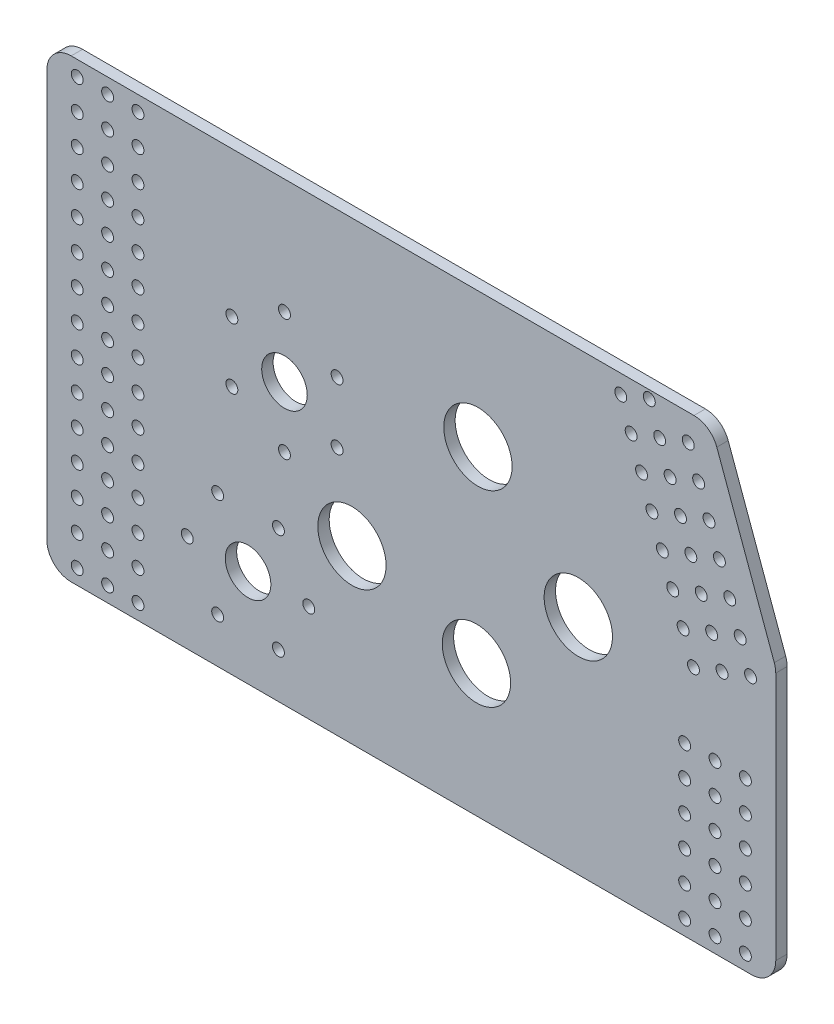
SolidWorks part; units mm, degrees
ref_plane "Front Plane" through (0, 0, 0) normal (0, 0, 1) x (1, 0, 0)
ref_plane "Top Plane" through (0, 0, 0) normal (0, 1, 0) x (1, 0, 0)
ref_plane "Right Plane" through (0, 0, 0) normal (1, 0, 0) x (0, 0, -1)
sketch "Sketch1" plane through (0, 0, 0) normal (0, 0, 1) x (1, 0, 0)
  line B0 (-152.4, 0) -> (152.4, 0)
  line B1 (152.4, 0) -> (152.4, 116.0843)
  line B2 (152.4, 116.0843) -> (125.3149, 190.5)
  line B3 (125.3149, 190.5) -> (-152.4, 190.5)
  line B4 (-152.4, 190.5) -> (-152.4, 0)
  circle B5 centre (-139.7, 184.15) radius 2.4892
  circle B6 centre (-127, 184.15) radius 2.4892
  circle B7 centre (-114.3, 184.15) radius 2.4892
  circle B8 centre (-127, 171.45) radius 2.4892
  circle B9 centre (-114.3, 171.45) radius 2.4892
  circle B10 centre (-127, 158.75) radius 2.4892
  circle B11 centre (-114.3, 158.75) radius 2.4892
  circle B12 centre (-127, 146.05) radius 2.4892
  circle B13 centre (-114.3, 146.05) radius 2.4892
  circle B14 centre (-127, 133.35) radius 2.4892
  circle B15 centre (-114.3, 133.35) radius 2.4892
  circle B16 centre (-127, 120.65) radius 2.4892
  circle B17 centre (-114.3, 120.65) radius 2.4892
  circle B18 centre (-127, 107.95) radius 2.4892
  circle B19 centre (-114.3, 107.95) radius 2.4892
  circle B20 centre (-127, 95.25) radius 2.4892
  circle B21 centre (-114.3, 95.25) radius 2.4892
  circle B22 centre (-127, 82.55) radius 2.4892
  circle B23 centre (-114.3, 82.55) radius 2.4892
  circle B24 centre (-127, 69.85) radius 2.4892
  circle B25 centre (-114.3, 69.85) radius 2.4892
  circle B26 centre (-127, 57.15) radius 2.4892
  circle B27 centre (-114.3, 57.15) radius 2.4892
  circle B28 centre (-127, 44.45) radius 2.4892
  circle B29 centre (-114.3, 44.45) radius 2.4892
  circle B30 centre (-127, 31.75) radius 2.4892
  circle B31 centre (-114.3, 31.75) radius 2.4892
  circle B32 centre (-127, 19.05) radius 2.4892
  circle B33 centre (-114.3, 19.05) radius 2.4892
  circle B34 centre (-127, 6.35) radius 2.4892
  circle B35 centre (-114.3, 6.35) radius 2.4892
  circle B36 centre (-139.7, 171.45) radius 2.4892
  circle B37 centre (-139.7, 158.75) radius 2.4892
  circle B38 centre (-139.7, 146.05) radius 2.4892
  circle B39 centre (-139.7, 133.35) radius 2.4892
  circle B40 centre (-139.7, 120.65) radius 2.4892
  circle B41 centre (-139.7, 107.95) radius 2.4892
  circle B42 centre (-139.7, 95.25) radius 2.4892
  circle B43 centre (-139.7, 82.55) radius 2.4892
  circle B44 centre (-139.7, 69.85) radius 2.4892
  circle B45 centre (-139.7, 57.15) radius 2.4892
  circle B46 centre (-139.7, 44.45) radius 2.4892
  circle B47 centre (-139.7, 31.75) radius 2.4892
  circle B48 centre (-139.7, 19.05) radius 2.4892
  circle B49 centre (-139.7, 6.35) radius 2.4892
  circle B50 centre (87.5907, 182.7494) radius 2.4892
  circle B51 centre (99.5248, 187.093) radius 2.4892
  circle B52 centre (115.8026, 179.5026) radius 2.4892
  circle B53 centre (91.9344, 170.8153) radius 2.4892
  circle B54 centre (103.8685, 175.1589) radius 2.4892
  circle B55 centre (120.1462, 167.5685) radius 2.4892
  circle B56 centre (96.278, 158.8812) radius 2.4892
  circle B57 centre (108.2121, 163.2248) radius 2.4892
  circle B58 centre (124.4899, 155.6344) radius 2.4892
  circle B59 centre (100.6217, 146.9471) radius 2.4892
  circle B60 centre (112.5558, 151.2907) radius 2.4892
  circle B61 centre (128.8335, 143.7003) radius 2.4892
  circle B62 centre (104.9653, 135.013) radius 2.4892
  circle B63 centre (116.8994, 139.3566) radius 2.4892
  circle B64 centre (133.1772, 131.7662) radius 2.4892
  circle B65 centre (109.309, 123.0789) radius 2.4892
  circle B66 centre (121.2431, 127.4226) radius 2.4892
  circle B67 centre (137.5208, 119.8321) radius 2.4892
  circle B68 centre (113.6526, 111.1448) radius 2.4892
  circle B69 centre (125.5867, 115.4885) radius 2.4892
  circle B70 centre (141.8645, 107.898) radius 2.4892
  circle B71 centre (117.9963, 99.2107) radius 2.4892
  circle B72 centre (129.9304, 103.5544) radius 2.4892
  circle B73 centre (146.2081, 95.9639) radius 2.4892
  circle B74 centre (114.3, 69.85) radius 2.4892
  circle B75 centre (127, 69.85) radius 2.4892
  circle B76 centre (139.7, 69.85) radius 2.4892
  circle B77 centre (114.3, 57.15) radius 2.4892
  circle B78 centre (127, 57.15) radius 2.4892
  circle B79 centre (139.7, 57.15) radius 2.4892
  circle B80 centre (114.3, 44.45) radius 2.4892
  circle B81 centre (127, 44.45) radius 2.4892
  circle B82 centre (139.7, 44.45) radius 2.4892
  circle B83 centre (114.3, 31.75) radius 2.4892
  circle B84 centre (127, 31.75) radius 2.4892
  circle B85 centre (139.7, 31.75) radius 2.4892
  circle B86 centre (114.3, 19.05) radius 2.4892
  circle B87 centre (127, 19.05) radius 2.4892
  circle B88 centre (139.7, 19.05) radius 2.4892
  circle B89 centre (114.3, 6.35) radius 2.4892
  circle B90 centre (127, 6.35) radius 2.4892
  circle B91 centre (139.7, 6.35) radius 2.4892
  circle B92 centre (11.8508, 132.0168) radius 14.2875
  circle B93 centre (-24.8197, 71.7449) radius 14.2875
  circle B94 centre (57.6351, 95.7125) radius 14.2875
  circle B95 centre (23.7546, 49.6787) radius 14.2875
  circle B96 centre (-65.2702, 36.9534) radius 9.525
  circle B97 centre (-65.2702, 106.5494) radius 9.525
  circle B98 centre (-65.2702, 131.9494) radius 2.4892
  circle B99 centre (-65.2702, 11.5534) radius 2.4892
  circle B100 centre (-43.2731, 119.2494) radius 2.4892
  circle B101 centre (-43.2731, 93.8494) radius 2.4892
  circle B102 centre (-65.2702, 81.1494) radius 2.4892
  circle B103 centre (-87.2672, 93.8494) radius 2.4892
  circle B104 centre (-87.2672, 119.2494) radius 2.4892
  circle B105 centre (-87.2672, 24.2534) radius 2.4892
  circle B106 centre (-87.2672, 49.6534) radius 2.4892
  circle B107 centre (-65.2702, 62.3534) radius 2.4892
  circle B108 centre (-43.2731, 49.6534) radius 2.4892
  circle B109 centre (-43.2731, 24.2534) radius 2.4892
sketch_block_instance "Block-InnerPlate-1"
sketch_block "Block-InnerPlate" parameters "D1"=4.9784, "D7"=4.9784, "D8"=4.9784, "D9"=4.9784, "D11"=4.9784, "D12"=4.9784, "D13"=4.9784, "D15"=19.05, "D16"=19.05, "D17"=28.575, "D18"=28.575, "D19"=28.575, "D20"=28.575, "D21"=4.9784, "D22"=4.9784, "D2"=6.35, "D3"=12.7, "D4"=12.7, "D5"=12.7, "D6"=6.35, "D10"=12.7, "D14"=12.7, "D23"=25.4, "D24"=25.4
extrude "Boss-Extrude1" add sketch "Sketch1" along normal blind 4.7625
sketch "Sketch2" plane through (0, 0, 4.7625) normal (0, 0, 1) x (1, 0, 0)
  circle A0 centre (146.2081, 95.9639) radius 2.4892
  dimension "D1" = 4.9784
extrude "Boss-Extrude2" add sketch "Sketch2" against normal blind 3.175
fillet "Fillet1" radius 10.16 5 edges at (-152.4, 0, 2.3813) (152.4, 0, 2.3813) (152.4, 116.0843, 2.3813) (125.3149, 190.5, 2.3813) (-152.4, 190.5, 2.3813)
sketch "Sketch3" plane through (0, 0, 4.7625) normal (0, 0, 1) x (1, 0, 0)
  line L0 (-65.2702, 106.5494) -> (-39.8702, 106.5494) construction
  line L1 (-65.2702, 36.9534) -> (-39.8702, 36.9534) construction
  circle A0 centre (-65.2702, 106.5494) radius 9.525
  circle A1 centre (-39.8702, 106.5494) radius 2.4892
  circle A2 centre (-52.5702, 84.5524) radius 2.4892
  circle A3 centre (-77.9702, 84.5524) radius 2.4892
  circle A4 centre (-90.6702, 106.5494) radius 2.4892
  circle A5 centre (-77.9702, 128.5465) radius 2.4892
  circle A6 centre (-52.5702, 128.5465) radius 2.4892
  circle A7 centre (-65.2702, 36.9534) radius 9.525
  circle A8 centre (-39.8702, 36.9534) radius 2.4892
  circle A9 centre (-52.5702, 14.9564) radius 2.4892
  circle A10 centre (-77.9702, 14.9564) radius 2.4892
  circle A11 centre (-90.6702, 36.9534) radius 2.4892
  circle A12 centre (-77.9702, 58.9505) radius 2.4892
  circle A13 centre (-52.5702, 58.9505) radius 2.4892
  dimension "D1" = 19.05
  dimension "D2" = 4.9784
  dimension "D7" = 19.05
  dimension "D8" = 4.9784
  dimension "D3" = 25.4
  dimension "D5" = 25.4
  dimension "D6" = 25.4
  dimension "D9" = 25.4
  dimension "D11" = 25.4
  dimension "D4" = 6
  dimension "D10" = 6
extrude "Cut-Extrude1" cut sketch "Sketch3" against normal blind 3.175
sketch "Sketch4" plane through (0, 0, 4.7625) normal (0, 0, 1) x (1, 0, 0)
  circle A0 centre (-65.2702, 131.9494) radius 2.4892
  circle A1 centre (-43.2731, 119.2494) radius 2.4892
  circle A2 centre (-43.2731, 93.8494) radius 2.4892
  circle A3 centre (-65.2702, 81.1494) radius 2.4892
  circle A4 centre (-87.2672, 93.8494) radius 2.4892
  circle A5 centre (-87.2672, 119.2494) radius 2.4892
  circle A6 centre (-65.2702, 62.3534) radius 2.4892
  circle A7 centre (-43.2731, 49.6534) radius 2.4892
  circle A8 centre (-43.2731, 24.2534) radius 2.4892
  circle A9 centre (-65.2702, 11.5534) radius 2.4892
  circle A10 centre (-87.2672, 24.2534) radius 2.4892
  circle A11 centre (-87.2672, 49.6534) radius 2.4892
  dimension "D1" = 4.9784
  dimension "D2" = 4.9784
  dimension "D3" = 4.9784
  dimension "D4" = 4.9784
  dimension "D5" = 4.9784
  dimension "D6" = 4.9784
  dimension "D7" = 4.9784
  dimension "D8" = 4.9784
  dimension "D9" = 4.9784
  dimension "D10" = 4.9784
  dimension "D11" = 4.9784
  dimension "D12" = 4.9784
extrude "Boss-Extrude3" add sketch "Sketch4" against normal blind 3.175
sketch "Sketch6" plane through (0, 0, 4.7625) normal (0, 0, 1) x (1, 0, 0)
  circle A0 centre (23.7546, 49.6787) radius 14.2875 construction
  circle A1 centre (57.6351, 95.7125) radius 14.2875 construction
  circle A2 centre (11.8508, 132.0168) radius 14.2875 construction
  circle A3 centre (23.7546, 49.6787) radius 14.2875
  circle A4 centre (57.6351, 95.7125) radius 14.2875
  circle A5 centre (11.8508, 132.0168) radius 14.2875
  circle A6 centre (-39.8702, 36.9534) radius 2.4892 construction
  circle A7 centre (-52.5702, 14.9564) radius 2.4892 construction
  circle A8 centre (-77.9702, 14.9564) radius 2.4892 construction
  circle A9 centre (-65.2702, 36.9534) radius 9.525 construction
  circle A10 centre (-90.6702, 36.9534) radius 2.4892 construction
  circle A11 centre (-52.5702, 58.9505) radius 2.4892 construction
  circle A12 centre (-77.9702, 58.9505) radius 2.4892 construction
  circle A13 centre (-52.5702, 84.5524) radius 2.4892 construction
  circle A14 centre (-77.9702, 84.5524) radius 2.4892 construction
  circle A15 centre (-90.6702, 106.5494) radius 2.4892 construction
  circle A16 centre (-65.2702, 106.5494) radius 9.525 construction
  circle A17 centre (-39.8702, 106.5494) radius 2.4892 construction
  circle A18 centre (-52.5702, 128.5465) radius 2.4892 construction
  circle A19 centre (-77.9702, 128.5465) radius 2.4892 construction
  circle A20 centre (-39.8702, 36.9534) radius 2.4892
  circle A21 centre (-52.5702, 14.9564) radius 2.4892
  circle A22 centre (-77.9702, 14.9564) radius 2.4892
  circle A23 centre (-65.2702, 36.9534) radius 9.525
  circle A24 centre (-90.6702, 36.9534) radius 2.4892
  circle A25 centre (-52.5702, 58.9505) radius 2.4892
  circle A26 centre (-77.9702, 58.9505) radius 2.4892
  circle A27 centre (-52.5702, 84.5524) radius 2.4892
  circle A28 centre (-77.9702, 84.5524) radius 2.4892
  circle A29 centre (-90.6702, 106.5494) radius 2.4892
  circle A30 centre (-65.2702, 106.5494) radius 9.525
  circle A31 centre (-39.8702, 106.5494) radius 2.4892
  circle A32 centre (-52.5702, 128.5465) radius 2.4892
  circle A33 centre (-77.9702, 128.5465) radius 2.4892
extrude "Boss-Extrude4" add sketch "Sketch6" against normal up to surface (4.7625 mm away) up to face at (25.4598, 99.6963, 0)
sketch "Sketch5" plane through (0, 0, 4.7625) normal (0, 0, 1) x (1, 0, 0)
  circle A1 centre (-24.8197, 71.7449) radius 14.2875
  circle A2 centre (-24.8197, 71.7449) radius 13.97
  circle A3 centre (27.2348, 55.2349) radius 40.64
  circle A4 centre (27.2348, 55.2349) radius 14.2875
  circle A5 centre (27.2348, 55.2349) radius 22.86
  circle A6 centre (69.8319, 93.3349) radius 34.29
  circle A7 centre (69.8319, 93.3349) radius 14.2875
  circle A8 centre (69.8319, 93.3349) radius 12.7
  circle A9 centre (27.8642, 133.9749) radius 45.72
  circle A10 centre (27.8642, 133.9749) radius 14.2875
  circle A11 centre (-24.8197, 71.7449) radius 14.2875 construction
  dimension "D1" = 27.94
  dimension "D2" = 81.28
  dimension "D3" = 28.575
  dimension "D4" = 45.72
  dimension "D5" = 68.58
  dimension "D6" = 28.575
  dimension "D7" = 25.4
  dimension "D8" = 91.44
  dimension "D12" = 28.575
  dimension "D9" = 16.51
  dimension "D10" = 38.1
  dimension "D11" = 40.64
extrude "Cut-Extrude2" cut sketch "Sketch5" against normal through all contours A4 | A9 A7 A8 | A8 | A7 A9 | A10 region at (69.8319, 93.3349, 4.7625) region at (58.9004, 99.8547, 4.7625) region at (60.198, 102.664, 4.7625) region at (27.2348, 55.2349, 4.7625) region at (27.8642, 133.9749, 4.7625)
sketch "Sketch7" plane through (0, 0, 0) normal (0, 0, 1) x (1, 0, 0)
  circle A0 centre (-55.5743, 18.8147) radius 2.4892
  circle A1 centre (-24.8197, 71.7449) radius 14.2875
  circle A2 centre (-24.8197, 71.7449) radius 45.72 construction
  circle A3 centre (-53.0343, 117.0118) radius 7.62 construction
  circle A4 centre (-24.8197, 71.7449) radius 14.2875 construction
  circle A5 centre (-68.2743, 40.8118) radius 7.62 construction
  circle A6 centre (-53.0343, 117.0118) radius 32.5374 construction
  circle A7 centre (-80.9743, 18.8147) radius 2.4892
  circle A8 centre (-68.2743, 40.8118) radius 32.5374 construction
  circle A9 centre (-93.6743, 40.8118) radius 2.4892
  circle A10 centre (-68.2743, 40.8118) radius 9.525
  circle A11 centre (-42.8743, 40.8118) radius 2.4892
  circle A12 centre (-55.5743, 62.8088) radius 2.4892
  circle A13 centre (-80.9743, 62.8088) radius 2.4892
  circle A14 centre (-31.0373, 104.3118) radius 2.4892
  circle A15 centre (-53.0343, 91.6118) radius 2.4892
  circle A16 centre (-75.0314, 104.3118) radius 2.4892
  circle A17 centre (-53.0343, 117.0118) radius 9.525
  circle A18 centre (-31.0373, 129.7118) radius 2.4892
  circle A19 centre (-53.0343, 142.4118) radius 2.4892
  circle A20 centre (-75.0314, 129.7118) radius 2.4892
  dimension "D1" = 91.44
  dimension "D2" = 15.24
  dimension "D5" = 65.0748
  dimension "D6" = 65.0748
  dimension "D7" = 19.05
  dimension "D8" = 4.9784
  dimension "D9" = 25.4
  dimension "D10" = 25.4
  dimension "D11" = 25.4
  dimension "D14" = 25.4
  dimension "D15" = 25.4
  dimension "D16" = 25.4
  dimension "D17" = 25.4
  dimension "D18" = 25.4
  dimension "D19" = 19.05
  dimension "D20" = 4.9784
  dimension "D3" = 76.2
  dimension "D4" = 15.24
  dimension "D12" = 25.4
  dimension "D13" = 25.4
  dimension "D21" = 25.4
  dimension "D22" = 25.4
  dimension "D23" = 25.4
  dimension "D24" = 25.4
  dimension "D25" = 25.4
  dimension "D26" = 25.4
  dimension "D27" = 25.4
  dimension "D28" = 25.4
  dimension "D29" = 25.4
  dimension "D30" = 25.4
  dimension "D31" = 25.4
extrude "Cut-Extrude3" cut sketch "Sketch7" along normal through all contours A9 | A13 | A11 | A12 | A7 | A0 | A10 | A20 | A17 | A19 | A15 | A14 | A18 | A16 region at (-55.5743, 18.8147, 0) region at (-80.9743, 18.8147, 0) region at (-93.6743, 40.8118, 0) region at (-68.2743, 40.8118, 0) region at (-42.8743, 40.8118, 0) region at (-55.5743, 62.8088, 0) region at (-80.9743, 62.8088, 0) region at (-31.0373, 104.3118, 0) region at (-53.0343, 91.6118, 0) region at (-53.0343, 117.0118, 0) region at (-31.0373, 129.7118, 0) region at (-53.0343, 142.4118, 0) region at (-75.0314, 129.7118, 0)
